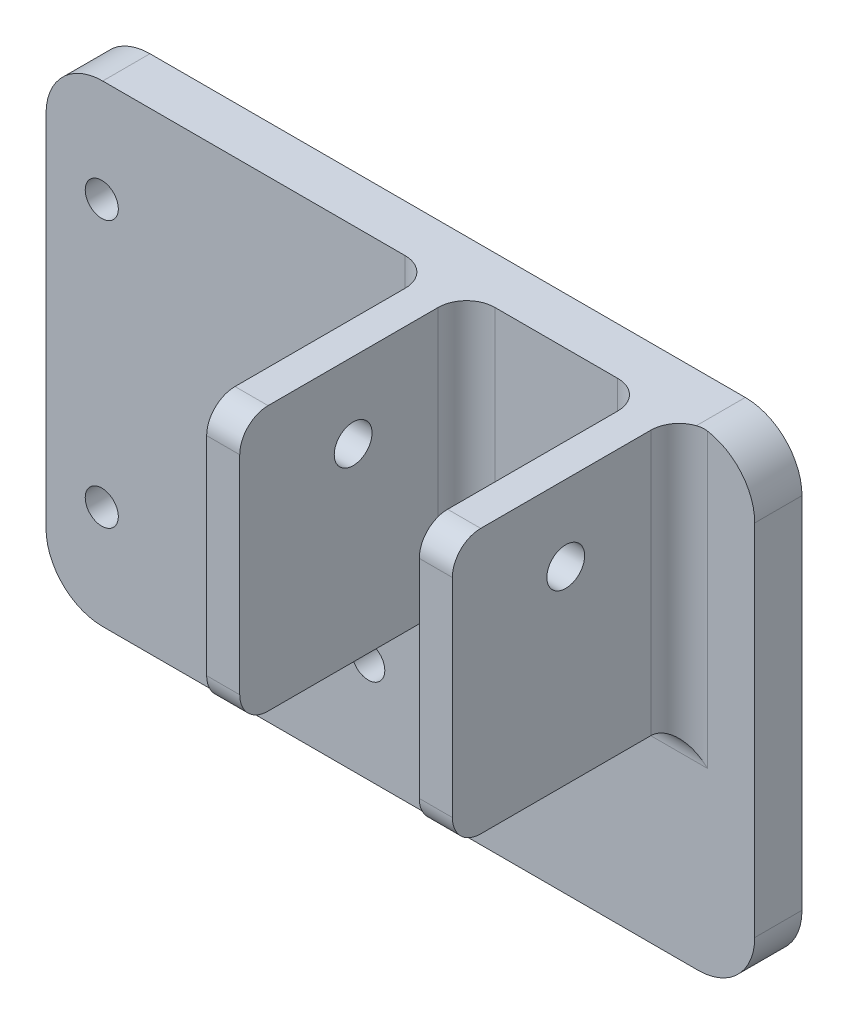
SolidWorks part; units mm, degrees
ref_plane "前视基准面" through (0, 0, 0) normal (0, 0, 1) x (1, 0, 0)
ref_plane "上视基准面" through (0, 0, 0) normal (0, 1, 0) x (1, 0, 0)
ref_plane "右视基准面" through (0, 0, 0) normal (1, 0, 0) x (0, 0, -1)
sketch "Sketch1" plane through (0, 0, 0) normal (0, 0, 1) x (1, 0, 0)
  line L1 (-13, -14) -> (13, -14)
  line L2 (-13, -14) -> (-13, 14)
  line L3 (-13, 14) -> (13, 14)
  line L4 (13, -14) -> (13, 14)
  line L5 (-13, -14) -> (13, 14) construction
  line L6 (-13, 14) -> (13, -14) construction
  line L7 (-9.5, -14) -> (9.5, -14)
  line L8 (-9.5, -14) -> (-9.5, 14)
  line L9 (-9.5, 14) -> (9.5, 14)
  line L10 (9.5, -14) -> (9.5, 14)
  line L11 (-9.5, -14) -> (9.5, 14) construction
  line L12 (-9.5, 14) -> (9.5, -14) construction
  point P0 (0, 0)
  point P6 (0, 0)
  dimension "D1" = 19
  dimension "D2" = 3.5
  dimension "D3" = 28
extrude "Boss-Extrude1" add sketch "Sketch1" along normal blind 24 contours L1 L8 L3 L2 | L10 L1 L4 L3 region at (-11.25, 0, 0) region at (11.25, 0, 0)
sketch "Sketch2" plane through (0, 0, 0) normal (0, 0, -1) x (-1, 0, 0)
  line L4 (-21, 14) -> (-21, -36)
  line L5 (-21, 14) -> (54, 14)
  line L6 (-21, -36) -> (54, -36)
  line L7 (54, 14) -> (54, -36)
  line L9 (-13, -14) -> (-13, 14) construction
  line L10 (-9.5, 14) -> (-13, 14) construction
  point P10 (56.7841, -34.8918)
  dimension "D1" = 50
  dimension "D2" = 8
  dimension "D3" = 75
extrude "Boss-Extrude2" add sketch "Sketch2" along normal blind 5
fillet "Fillet1" radius 6 4 edges at (-54, -36, -2.5) (-54, 14, -2.5) (21, 14, -2.5) (21, -36, -2.5)
fillet "Fillet2" radius 3 10 edges at (11.25, -14, 24) (11.25, 14, 24) (-11.25, 14, 24) (-11.25, -14, 24) (-11.25, -14, 0) (11.25, -14, 0) (-13, 0, 0) (13, 0, 0) (-9.5, 0, 0) (9.5, 0, 0)
sketch "Sketch3" plane through (13, 0, 0) normal (1, 0, 0) x (0, 0, -1)
  line L0 (-24, -11) -> (-24, 11) construction
  line L1 (-21, 14) -> (-3, 14) construction
  circle A0 centre (-12, 6) radius 2
  dimension "D1" = 12
  dimension "D2" = 8
  dimension "D3" = 4
extrude "Cut-Extrude1" cut sketch "Sketch3" against normal through all both and the other way through all
sketch "Sketch4" plane through (0, 0, -5) normal (0, 0, -1) x (-1, 0, 0)
  line L0 (54, -11) -> (34, -11) construction
  line L1 (48.1, -25.1) -> (19.9, -25.1) construction
  line L2 (48.1, -25.1) -> (48.1, 3.1) construction
  line L3 (48.1, 3.1) -> (19.9, 3.1) construction
  line L4 (19.9, -25.1) -> (19.9, 3.1) construction
  line L5 (48.1, -25.1) -> (19.9, 3.1) construction
  line L6 (48.1, 3.1) -> (19.9, -25.1) construction
  line L7 (54, -30) -> (54, 8) construction
  circle A0 centre (19.9, 3.1) radius 1.75
  circle A1 centre (48.1, 3.1) radius 1.75
  circle A2 centre (48.1, -25.1) radius 1.75
  circle A3 centre (19.9, -25.1) radius 1.75
  point P0 (34, -11)
  dimension "D1" = 3.5
  dimension "D2" = 28.2
  dimension "D3" = 20
extrude "Cut-Extrude2" cut sketch "Sketch4" against normal through all both and the other way through all
